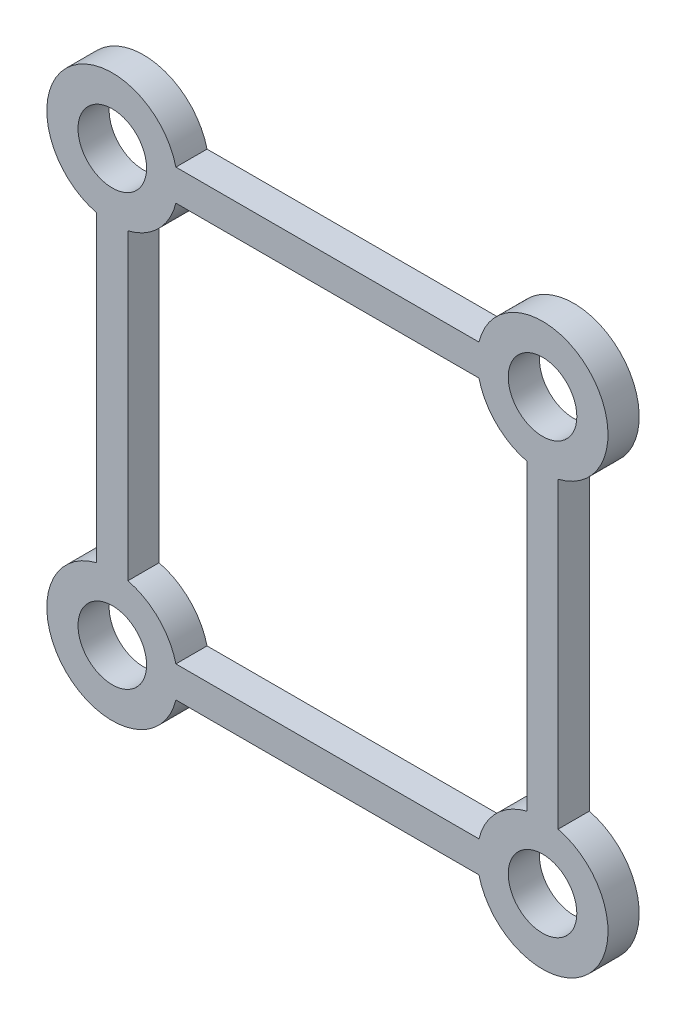
SolidWorks part; units mm, degrees
ref_plane "Front Plane" through (0, 0, 0) normal (1, 0, 0) x (0, 1, 0)
ref_plane "Top Plane" through (0, 0, 0) normal (0, 0, 1) x (0, 1, 0)
ref_plane "Right Plane" through (0, 0, 0) normal (0, 1, 0) x (-1, 0, 0)
ref_axis "x axis" through (-88.99, 0, 0) along (1, 0, 0)
ref_axis "y xxis" through (0, 88.99, 0) along (0, -1, 0)
ref_axis "z axis" through (0, 0, 55) along (0, 0, -1)
sketch "Sketch1" plane through (0, 0, 0) normal (0, 0, 1) x (0, 1, 0)
  line L1 (-6.9, -6.9) -> (6.9, -6.9) construction
  line L2 (-6.9, -6.9) -> (-6.9, 6.9) construction
  line L3 (-6.9, 6.9) -> (6.9, 6.9) construction
  line L4 (6.9, -6.9) -> (6.9, 6.9) construction
  line L5 (-6.9, -6.9) -> (6.9, 6.9) construction
  line L6 (-6.9, 6.9) -> (6.9, -6.9) construction
  line L7 (-4.8604, 6.4) -> (4.8604, 6.4)
  line L8 (6.4, -4.8604) -> (6.4, 4.8604)
  line L9 (-4.8604, -6.4) -> (4.8604, -6.4)
  line L11 (-4.8604, 7.4) -> (4.8604, 7.4)
  line L12 (7.4, -4.8604) -> (7.4, 4.8604)
  line L13 (-4.8604, -7.4) -> (4.8604, -7.4)
  line L14 (-7.4, 7.4) -> (7.4, 7.4) construction
  line L15 (-7.4, -7.4) -> (-7.4, 7.4) construction
  line L16 (-6.4, 6.4) -> (6.4, 6.4) construction
  line L17 (-6.4, -6.4) -> (-6.4, 6.4) construction
  line L18 (-7.4, -4.8604) -> (-7.4, 4.8604)
  line L19 (-6.4, -4.8604) -> (-6.4, 4.8604)
  line L20 (-6.4, -6.4) -> (6.4, -6.4) construction
  line L21 (-7.4, -7.4) -> (7.4, -7.4) construction
  line L22 (6.4, -6.4) -> (6.4, 6.4) construction
  line L24 (7.4, -7.4) -> (7.4, 7.4) construction
  circle A0 centre (-6.9, 6.9) radius 1.1
  circle A1 centre (6.9, 6.9) radius 1.1
  circle A2 centre (6.9, -6.9) radius 1.1
  circle A3 centre (-6.9, -6.9) radius 1.1
  arc A4 (-4.8604, 7.4) -> (-7.4, 4.8604) centre (-6.9, 6.9) ccw
  arc A5 (7.4, 4.8604) -> (4.8604, 7.4) centre (6.9, 6.9) ccw
  arc A6 (4.8604, -7.4) -> (7.4, -4.8604) centre (6.9, -6.9) ccw
  arc A7 (-7.4, -4.8604) -> (-4.8604, -7.4) centre (-6.9, -6.9) ccw
  circle A8 centre (-6.9, 6.9) radius 2.1 construction
  arc A9 (-6.4, 4.8604) -> (-4.8604, 6.4) centre (-6.9, 6.9) ccw
  circle A10 centre (-6.9, -6.9) radius 2.1 construction
  arc A11 (-4.8604, -6.4) -> (-6.4, -4.8604) centre (-6.9, -6.9) ccw
  circle A12 centre (6.9, -6.9) radius 2.1 construction
  arc A13 (6.4, -4.8604) -> (4.8604, -6.4) centre (6.9, -6.9) ccw
  circle A14 centre (6.9, 6.9) radius 2.1 construction
  arc A15 (4.8604, 6.4) -> (6.4, 4.8604) centre (6.9, 6.9) ccw
  point P0 (0, 0)
  dimension "D1" = 13.8
  dimension "D2" = 2.2
  dimension "D4" = 0.5
  dimension "D6" = 0.5
  dimension "D7" = 0.5
  dimension "D3" = 1
  dimension "D5" = 0.5
extrude "Boss-Extrude1" add sketch "Sketch1" along normal blind 1
